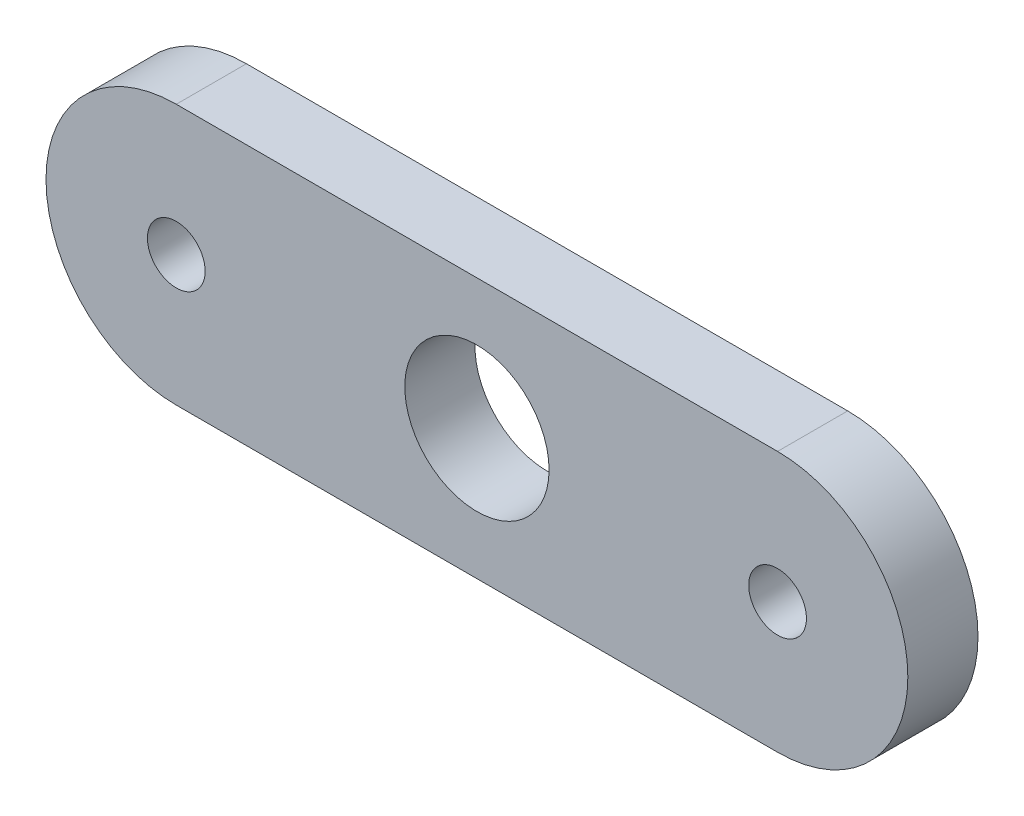
SolidWorks part; units mm, degrees
ref_plane "前视基准面" through (0, 0, 0) normal (0, 0, 1) x (1, 0, 0)
ref_plane "上视基准面" through (0, 0, 0) normal (0, 1, 0) x (1, 0, 0)
ref_plane "右视基准面" through (0, 0, 0) normal (1, 0, 0) x (0, 0, -1)
sketch "草图1" plane through (0, 0, 0) normal (0, 0, 1) x (1, 0, 0)
  line L0 (-15, 0) -> (15, 0) construction
  line L1 (-15, 6.5) -> (15, 6.5)
  line L2 (-15, -6.5) -> (15, -6.5)
  arc A0 (-15, 6.5) -> (-15, -6.5) centre (-15, 0) ccw
  arc A1 (15, -6.5) -> (15, 6.5) centre (15, 0) ccw
  circle A2 centre (-15, 0) radius 1.44
  circle A3 centre (15, 0) radius 1.44
  circle A4 centre (0, 0) radius 3.6
  point P2 (0, 0)
  dimension "D1" = 6.5
  dimension "D3" = 2.88
  dimension "D4" = 2.88
  dimension "D5" = 7.2
  dimension "D2" = 30
extrude "凸台-拉伸2" add sketch "草图1" along normal blind 2
extrude "凸台-拉伸3" add sketch "草图1<2>" along normal blind 3.5
sketch "草图1<2>" plane through (0, 0, 0) normal (0, 0, 1) x (1, 0, 0) same geometry as "草图1"
